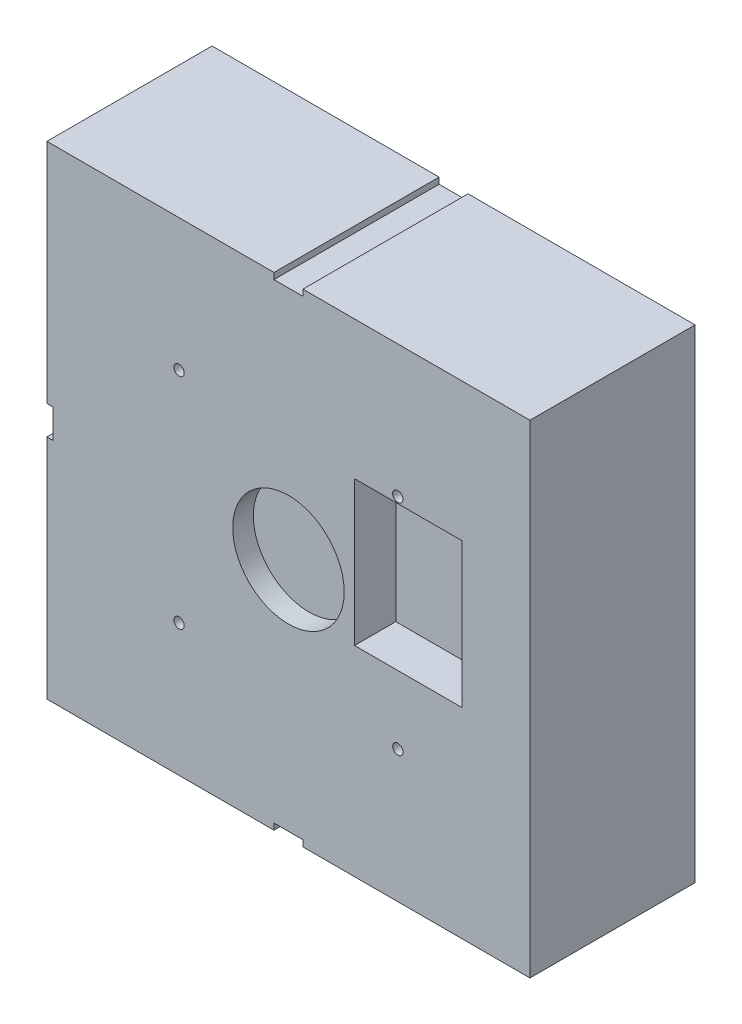
SolidWorks part; units mm, degrees
ref_plane "Front" through (0, 0, 0) normal (0, 0, 1) x (1, 0, 0)
ref_plane "Top" through (0, 0, 0) normal (0, 1, 0) x (1, 0, 0)
ref_plane "Right" through (0, 0, 0) normal (1, 0, 0) x (0, 0, -1)
sketch "Sketch1" plane through (0, 0, 0) normal (0, 0, 1) x (1, 0, 0)
  line L1 (-58.5, 58.5) -> (58.5, 58.5)
  line L2 (-58.5, 58.5) -> (-58.5, -58.5)
  line L3 (-58.5, -58.5) -> (58.5, -58.5)
  line L4 (58.5, 58.5) -> (58.5, -58.5)
  line L5 (-58.5, 58.5) -> (58.5, -58.5) construction
  line L6 (-58.5, -58.5) -> (58.5, 58.5) construction
  point P0 (0, 0)
  dimension "D1" = 117
  dimension "D2" = 117
extrude "body" add sketch "Sketch1" along normal blind 40
ref_point "Point1"
ref_axis "Axis1" through (0, 0, 0) along (0, 0, -1)
sketch "Sketch4" plane through (0, 0, 0) normal (0, 0, -1) x (-1, 0, 0)
  line L0 (-58.5, 58.5) -> (58.5, 58.5) construction
  line L1 (3.5, 57) -> (-3.5, 57)
  line L2 (3.5, 57) -> (3.5, 60)
  line L3 (3.5, 60) -> (-3.5, 60)
  line L4 (-3.5, 57) -> (-3.5, 60)
  line L5 (3.5, 57) -> (-3.5, 60) construction
  line L6 (3.5, 60) -> (-3.5, 57) construction
  line L7 (57, -3.5) -> (60, -3.5)
  line L8 (57, -3.5) -> (57, 3.5)
  line L9 (57, 3.5) -> (60, 3.5)
  line L10 (60, -3.5) -> (60, 3.5)
  line L11 (-3.5, -57) -> (-3.5, -60)
  line L12 (-3.5, -57) -> (3.5, -57)
  line L13 (3.5, -57) -> (3.5, -60)
  line L14 (-3.5, -60) -> (3.5, -60)
  line L15 (-57, 3.5) -> (-60, 3.5)
  line L16 (-57, 3.5) -> (-57, -3.5)
  line L17 (-57, -3.5) -> (-60, -3.5)
  line L18 (-60, 3.5) -> (-60, -3.5)
  point P0 (0, 58.5)
  dimension "D1" = 7
  dimension "D2" = 3
  dimension "D3" = 4
extrude "rails housings" cut sketch "Sketch4" against normal through all
sketch "Sketch5" plane through (0, 0, 0) normal (0, 0, -1) x (-1, 0, 0)
  line L1 (48, -48) -> (-48, -48)
  line L2 (48, -48) -> (48, 48)
  line L3 (48, 48) -> (-48, 48)
  line L4 (-48, -48) -> (-48, 48)
  line L5 (48, -48) -> (-48, 48) construction
  line L6 (48, 48) -> (-48, -48) construction
  point P0 (0, 0)
  dimension "D1" = 96
  dimension "D2" = 96
sketch "Sketch6" plane through (0, 0, 0) normal (0, 0, -1) x (-1, 0, 0)
  line L0 (48, -48) -> (-48, 48) construction
  line L1 (-48, -48) -> (-48, 48) construction
  circle A0 centre (-26.5, 26.5) radius 1.25
  circle A1 centre (26.5, 26.5) radius 1.25
  circle A2 centre (26.5, -26.5) radius 1.25
  circle A3 centre (-26.5, -26.5) radius 1.25
  dimension "D4" = 2.5
  dimension "D1" = 21.5
  dimension "D2" = 2
  dimension "D3" = 2
extrude "drill holes" cut sketch "Sketch6" along normal blind 10 from surface starting at face at (0, 0, 40)
sketch "Sketch7" plane through (0, 0, 0) normal (0, 0, -1) x (-1, 0, 0)
  line L0 (48, 48) -> (-48, 48) construction
  line L1 (-16, -10) -> (-42, -10)
  line L2 (-16, -10) -> (-16, 25)
  line L3 (-16, 25) -> (-42, 25)
  line L4 (-42, -10) -> (-42, 25)
  line L5 (-16, -10) -> (-42, 25) construction
  line L6 (-16, 25) -> (-42, -10) construction
  line L7 (-48, -48) -> (-48, 48) construction
  point P0 (-29, 7.5)
  dimension "D1" = 35
  dimension "D2" = 26
  dimension "D3" = 23
  dimension "D4" = 32
extrude "PCB gap" cut sketch "Sketch7" along normal blind 10 from surface starting at face at (27.75, -26.5, 40)
sketch "Sketch8" plane through (0, 0, 0) normal (0, 0, -1) x (-1, 0, 0)
  circle A0 centre (0, 0) radius 13.5
  dimension "D1" = 27
extrude "motor gap" cut sketch "Sketch8" along normal blind 5 from surface starting at face at (29, 7.5, 40)
sketch "Sketch13" plane through (57, 0, 0) normal (1, 0, 0) x (0, 0, -1)
  line L1 (-40, -3.5) -> (0, -3.5)
  line L2 (-40, -3.5) -> (-40, 3.5)
  line L3 (-40, 3.5) -> (0, 3.5)
  line L4 (0, -3.5) -> (0, 3.5)
extrude "Boss-Extrude4" add sketch "Sketch13" along normal up to surface (1.5 mm away) up to face at (58.5, 31, 20)
